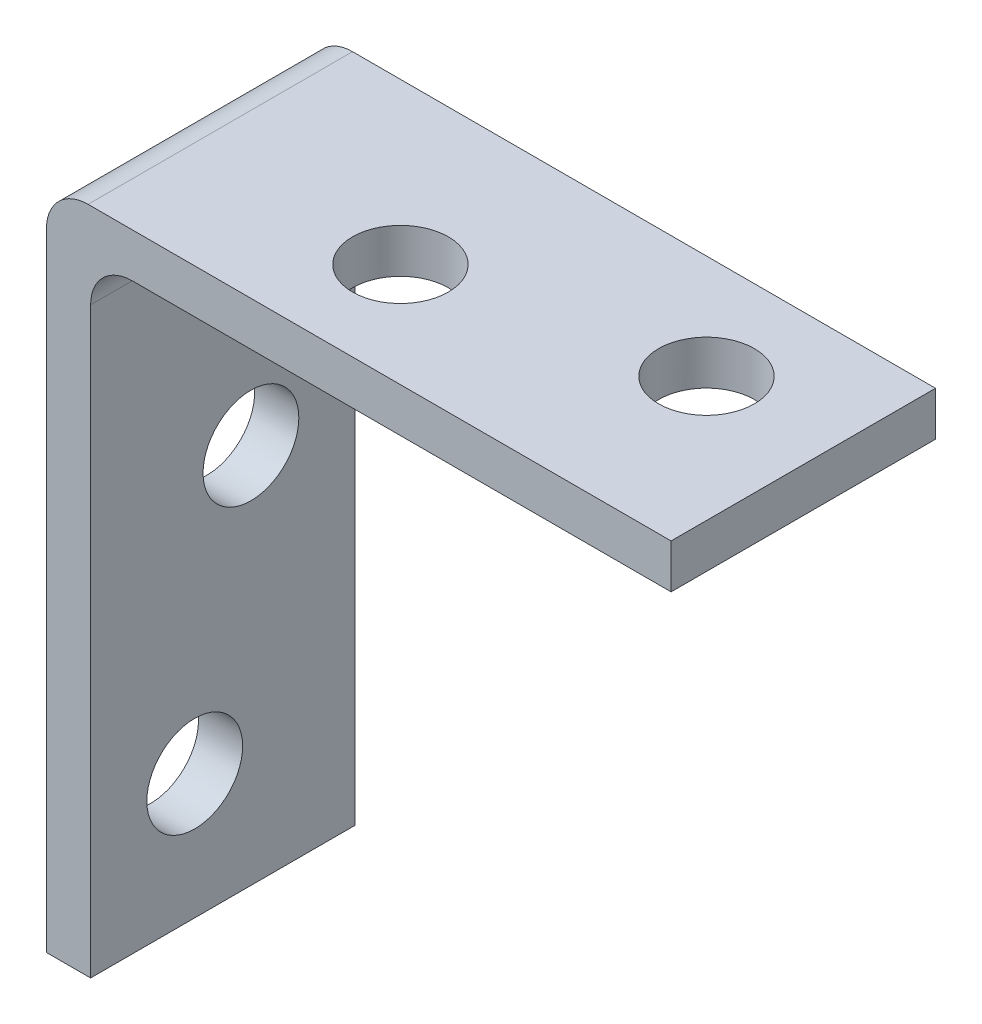
SolidWorks part; units mm, degrees
ref_plane "Front Plane" through (0, 0, 0) normal (0, 0, 1) x (1, 0, 0)
ref_plane "Top Plane" through (0, 0, 0) normal (0, 1, 0) x (1, 0, 0)
ref_plane "Right Plane" through (0, 0, 0) normal (1, 0, 0) x (0, 0, -1)
sketch "Sketch1" plane through (0, 0, 0) normal (0, 0, 1) x (1, 0, 0)
  line L1 (0, 0) -> (2.6924, 0)
  line L2 (0, 0) -> (0, 38.1)
  line L4 (2.6924, 0) -> (2.6924, 38.1)
  line L5 (2.6924, 38.1) -> (38.1, 38.1)
  line L6 (0, 38.1) -> (0, 40.7924)
  line L7 (0, 40.7924) -> (38.1, 40.7924)
  line L8 (38.1, 38.1) -> (38.1, 40.7924)
  dimension "D1" = 38.1
  dimension "D2" = 2.6924
  dimension "D3" = 2.6924
extrude "Boss-Extrude1" add sketch "Sketch1" along normal blind 8.0645 and the other way blind 8.0645
sketch "Sketch2" plane through (0, 0, 0) normal (-1, 0, 0) x (0, 0, 1)
  line L0 (-8.0645, 0) -> (8.0645, 0) construction
  line L3 (8.0645, 0) -> (8.0645, 38.1) construction
  line L4 (-8.0645, 0) -> (-8.0645, 38.1) construction
  circle A0 centre (1.7145, 7.62) radius 2.921
  circle A1 centre (-1.7145, 23.241) radius 2.921
  dimension "D5" = 5.842
  dimension "D1" = 7.62
  dimension "D2" = 15.621
  dimension "D3" = 6.35
  dimension "D4" = 6.35
extrude "Cut-Extrude1" cut sketch "Sketch2" against normal up to next
sketch "Sketch5" plane through (0, 38.1, 0) normal (0, -1, 0) x (1, 0, 0)
  line L0 (2.6924, -8.0645) -> (38.1, -8.0645) construction
  line L1 (2.6924, 8.0645) -> (38.1, 8.0645) construction
  line L2 (38.1, -8.0645) -> (38.1, 8.0645) construction
  circle A0 centre (30.48, -1.7145) radius 2.921
  circle A1 centre (15.24, 1.7145) radius 2.921
  dimension "D5" = 5.842
  dimension "D1" = 6.35
  dimension "D2" = 6.35
  dimension "D3" = 7.62
  dimension "D4" = 15.24
extrude "Cut-Extrude2" cut sketch "Sketch5" against normal up to next
fillet "Fillet1" radius 2.54 2 edges at (0, 40.7924, 0) (2.6924, 38.1, 0)
